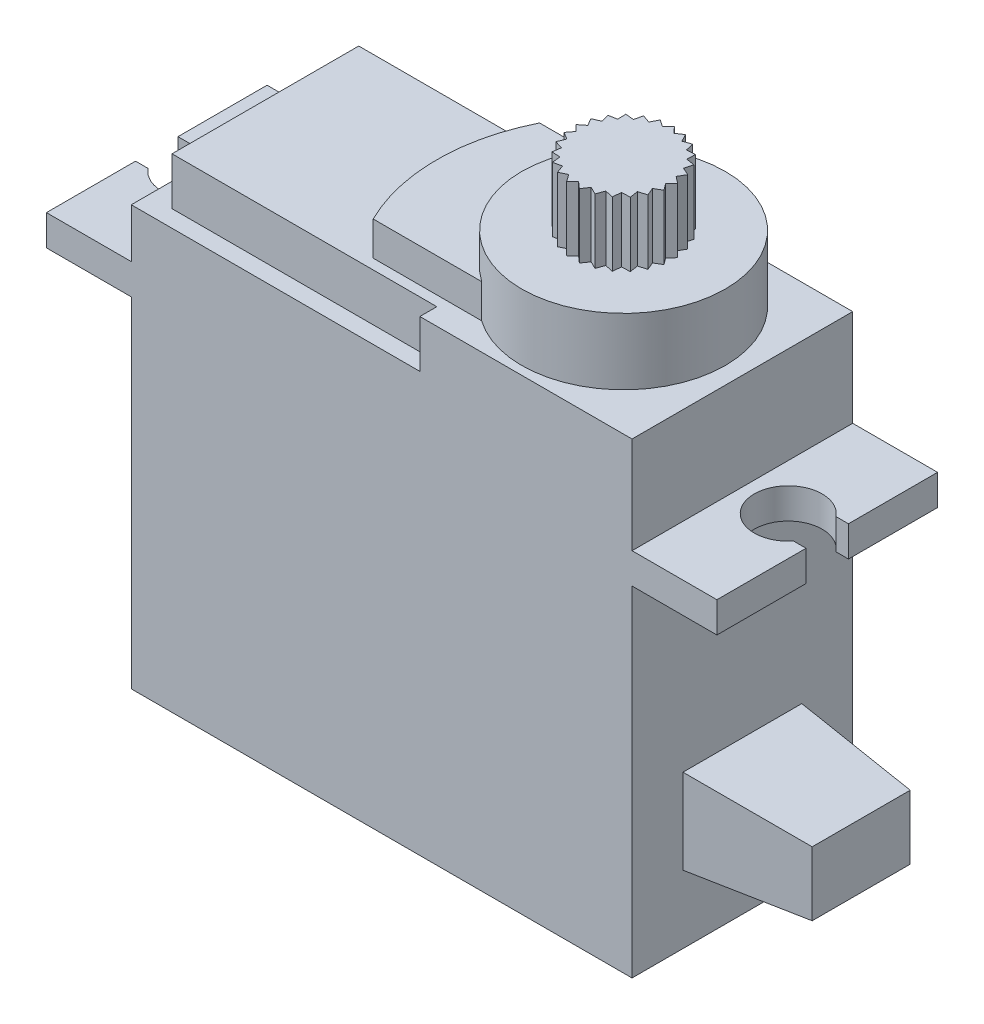
SolidWorks part; units mm, degrees
ref_plane "Plan de face" through (0, 0, 0) normal (0, 0, 1) x (1, 0, 0)
ref_plane "Plan de dessus" through (0, 0, 0) normal (0, 1, 0) x (1, 0, 0)
ref_plane "Plan de droite" through (0, 0, 0) normal (1, 0, 0) x (0, 0, -1)
sketch "Esquisse1" plane through (0, 0, 0) normal (0, 0, 1) x (1, 0, 0)
  line L0 (-22.5, -11.2) -> (-22.5, -31.2)
  line L1 (-22.5, -3.7) -> (7, -3.7)
  line L2 (-22.5, -3.7) -> (-22.5, -9.4)
  line L3 (-22.5, -31.2) -> (7, -31.2)
  line L4 (7, -3.7) -> (7, -9.4)
  line L5 (-22.5, -9.4) -> (-27.5, -9.4)
  line L6 (7, -11.2) -> (7, -31.2)
  line L7 (-22.5, -11.2) -> (-27.5, -11.2)
  line L8 (-27.5, -9.4) -> (-27.5, -11.2)
  line L9 (7, -11.2) -> (12, -11.2)
  line L11 (7, -9.4) -> (12, -9.4)
  line L12 (12, -11.2) -> (12, -9.4)
  dimension "D1" = 29.5
  dimension "D2" = 27.5
  dimension "D3" = 31.2
  dimension "D4" = 20
  dimension "D5" = 5
  dimension "D6" = 5
  dimension "D7" = 7
extrude "Boss.-Extru.1" add sketch "Esquisse1" along normal blind 6.5 and the other way blind 6.5
sketch "Esquisse2" plane through (0, -3.7, 0) normal (0, 1, 0) x (1, 0, 0)
  line L0 (-5.5, 6.5) -> (-5.5, 5.5)
  line L1 (7, 6.5) -> (-22.5, 6.5) construction
  line L2 (-5.5, 5.5) -> (-21.1, 5.5)
  line L3 (-21.1, 5.5) -> (-21.1, -5.5)
  line L4 (-21.1, -5.5) -> (-5.5, -5.5)
  line L5 (-5.5, -5.5) -> (-5.5, -6.5)
  line L6 (7, -6.5) -> (-22.5, -6.5) construction
  line L7 (-5.5, -6.5) -> (-22.5, -6.5)
  line L8 (-22.5, -6.5) -> (-22.5, 6.5)
  line L9 (-22.5, 6.5) -> (-5.5, 6.5)
  dimension "D1" = 1
  dimension "D2" = 1
  dimension "D3" = 17
  dimension "D4" = 1.4
extrude "Enlèv. mat.-Extru.1" cut sketch "Esquisse2" against normal blind 2.8
sketch "Esquisse3" plane through (0, -3.7, 0) normal (0, 1, 0) x (1, 0, 0)
  circle A0 centre (0, 0) radius 6
extrude "Boss.-Extru.2" add sketch "Esquisse3" along normal blind 3.9 contours A0
sketch "Esquisse4" plane through (0, 0.2, 0) normal (0, 1, 0) x (1, 0, 0)
  line L0 (0.3321, 2.6291) -> (0, 3)
  line L1 (0.7461, 2.9057) -> (0.3321, 2.6291)
  line L2 (0.9755, 2.4639) -> (0.7461, 2.9057)
  line L3 (1.4453, 2.6289) -> (0.9755, 2.4639)
  line L4 (1.5576, 2.1439) -> (1.4453, 2.6289)
  line L5 (2.0536, 2.1869) -> (1.5576, 2.1439)
  line L6 (2.0419, 1.6892) -> (2.0536, 2.1869)
  line L7 (2.533, 1.6075) -> (2.0419, 1.6892)
  line L8 (2.3978, 1.1283) -> (2.533, 1.6075)
  line L9 (2.8532, 0.9271) -> (2.3978, 1.1283)
  line L10 (2.6031, 0.4966) -> (2.8532, 0.9271)
  line L11 (2.9941, 0.1884) -> (2.6031, 0.4966)
  line L12 (2.6448, -0.1664) -> (2.9941, 0.1884)
  line L13 (2.9469, -0.5621) -> (2.6448, -0.1664)
  line L14 (2.5203, -0.8189) -> (2.9469, -0.5621)
  line L15 (2.7145, -1.2773) -> (2.5203, -0.8189)
  line L16 (2.2375, -1.4199) -> (2.7145, -1.2773)
  line L17 (2.3115, -1.9123) -> (2.2375, -1.4199)
  line L18 (1.814, -1.9318) -> (2.3115, -1.9123)
  line L19 (1.7634, -2.4271) -> (1.814, -1.9318)
  line L20 (1.2766, -2.3222) -> (1.7634, -2.4271)
  line L21 (1.1044, -2.7893) -> (1.2766, -2.3222)
  line L22 (0.659, -2.5667) -> (1.1044, -2.7893)
  line L23 (0.376, -2.9763) -> (0.659, -2.5667)
  line L24 (0, -2.65) -> (0.376, -2.9763)
  line L25 (-0.376, -2.9763) -> (0, -2.65)
  line L26 (-0.659, -2.5667) -> (-0.376, -2.9763)
  line L27 (-1.1044, -2.7893) -> (-0.659, -2.5667)
  line L28 (-1.2766, -2.3222) -> (-1.1044, -2.7893)
  line L29 (-1.7634, -2.4271) -> (-1.2766, -2.3222)
  line L30 (-1.814, -1.9318) -> (-1.7634, -2.4271)
  line L31 (-2.3115, -1.9123) -> (-1.814, -1.9318)
  line L32 (-2.2375, -1.4199) -> (-2.3115, -1.9123)
  line L33 (-2.7145, -1.2773) -> (-2.2375, -1.4199)
  line L34 (-2.5203, -0.8189) -> (-2.7145, -1.2773)
  line L35 (-2.9469, -0.5621) -> (-2.5203, -0.8189)
  line L36 (-2.6448, -0.1664) -> (-2.9469, -0.5621)
  line L37 (-2.9941, 0.1884) -> (-2.6448, -0.1664)
  line L38 (-2.6031, 0.4966) -> (-2.9941, 0.1884)
  line L39 (-2.8532, 0.9271) -> (-2.6031, 0.4966)
  line L40 (-2.3978, 1.1283) -> (-2.8532, 0.9271)
  line L41 (-2.533, 1.6075) -> (-2.3978, 1.1283)
  line L42 (-2.0419, 1.6892) -> (-2.533, 1.6075)
  line L43 (-2.0536, 2.1869) -> (-2.0419, 1.6892)
  line L44 (-1.5576, 2.1439) -> (-2.0536, 2.1869)
  line L45 (-1.4453, 2.6289) -> (-1.5576, 2.1439)
  line L46 (-0.9755, 2.4639) -> (-1.4453, 2.6289)
  line L47 (-0.7461, 2.9057) -> (-0.9755, 2.4639)
  line L50 (0, 3) -> (-0.3321, 2.6291)
  line L51 (-0.3321, 2.6291) -> (-0.7461, 2.9057)
  point P77 (0, 0)
  dimension "D1" = 25
extrude "Boss.-Extru.3" add sketch "Esquisse4" along normal blind 3.8
sketch "Esquisse5" plane through (0, -3.7, 0) normal (0, 1, 0) x (1, 0, 0)
  line L2 (-9.8484, 4.9) -> (0, 4.9)
  line L3 (0, 4.9) -> (0, -4.9)
  line L4 (0, -4.9) -> (-9.8484, -4.9)
  arc A0 (-9.8484, 4.9) -> (-9.8484, -4.9) centre (0, 0) ccw
  dimension "D1" = 22
  dimension "D2" = 9.8
extrude "Boss.-Extru.4" add sketch "Esquisse5" along normal blind 2
hole_wizard "Diamètre du perçage Ø4.0 (4)1" positions "Esquisse7" profile "Esquisse6" hole size "Ø4.0" standard "ISO" end condition through all
sketch "Esquisse7" plane through (0, -9.4, 0) normal (0, 1, 0) x (1, 0, 0)
  line L0 (-27.5, 6.5) -> (-27.5, -6.5) construction
  point P0 (-25.2, 0)
  dimension "D1" = 2.3
sketch "Esquisse6" plane through (-25.2, -9.4, 0) normal (1, 0, 0) x (0, 0, 1)
  line L0 (0, 0) -> (0, 21.8)
  line L1 (0, 21.8) -> (2, 21.8)
  line L2 (2, 21.8) -> (2, 0)
  line L5 (2, 0) -> (0, 0)
  line L11 (0, -6.35) -> (0, 107.95) construction
  dimension "Diamètre du perçage jusqu'au prochain" = 4
  dimension "Profondeur du perçage jusqu'au prochain" = 21.8
hole_wizard "Diamètre du perçage Ø4.0 (4)2" positions "Esquisse9" profile "Esquisse8" hole size "Ø4.0" standard "ISO" end condition through all
sketch "Esquisse9" plane through (0, -9.4, 0) normal (0, 1, 0) x (1, 0, 0)
  line L0 (12, 6.5) -> (12, -6.5) construction
  point P0 (9.7, 0)
  dimension "D1" = 2.3
sketch "Esquisse8" plane through (9.7, -9.4, 0) normal (1, 0, 0) x (0, 0, 1)
  line L0 (0, 0) -> (0, 21.8)
  line L1 (0, 21.8) -> (2, 21.8)
  line L2 (2, 21.8) -> (2, 0)
  line L5 (2, 0) -> (0, 0)
  line L11 (0, -6.35) -> (0, 107.95) construction
  dimension "Diamètre du perçage jusqu'au prochain" = 4
  dimension "Profondeur du perçage jusqu'au prochain" = 21.8
sketch "Esquisse10" plane through (7, 0, 0) normal (1, 0, 0) x (0, 0, -1)
  line L0 (6.5, -31.2) -> (-6.5, -31.2) construction
  line L1 (-3.5, -22.2) -> (3.5, -22.2)
  line L2 (-3.5, -22.2) -> (-3.5, -27.2)
  line L3 (-3.5, -27.2) -> (3.5, -27.2)
  line L4 (3.5, -22.2) -> (3.5, -27.2)
  dimension "D1" = 9
  dimension "D2" = 5
  dimension "D3" = 7
  dimension "D4" = 3.5
extrude "Boss.-Extru.5" add sketch "Esquisse10" along normal blind 7
draft "Dépouille1" type of draft neutral plane draft angle 5 faces to draft 4 face at (10.5, -27.2, 0) face at (10.5, -24.7, -3.5) face at (10.5, -22.2, 0) face at (10.5, -24.7, 3.5) neutral plane through (7, -11.2, -6.5) neutral plane normal (1, 0, 0) parameters "D1"=5
sketch "Esquisse11" plane through (0, -9.4, 0) normal (0, 1, 0) x (1, 0, 0)
  line L0 (-27.5, 6.5) -> (-27.5, -6.5) construction
  line L1 (-27.5, 1.25) -> (-25.5, 1.25)
  line L2 (-27.5, 1.25) -> (-27.5, -1.25)
  line L3 (-27.5, -1.25) -> (-25.5, -1.25)
  line L4 (-25.5, 1.25) -> (-25.5, -1.25)
  dimension "D1" = 1.25
  dimension "D2" = 2.5
extrude "Enlèv. mat.-Extru.2" cut sketch "Esquisse11" against normal through all
sketch "Esquisse12" plane through (0, -9.4, 0) normal (0, 1, 0) x (1, 0, 0)
  line L0 (12, 6.5) -> (12, -6.5) construction
  line L1 (12, 1.25) -> (10, 1.25)
  line L2 (12, 1.25) -> (12, -1.25)
  line L3 (12, -1.25) -> (10, -1.25)
  line L4 (10, 1.25) -> (10, -1.25)
  dimension "D1" = 2.5
  dimension "D2" = 1.25
extrude "Enlèv. mat.-Extru.3" cut sketch "Esquisse12" against normal up to next
